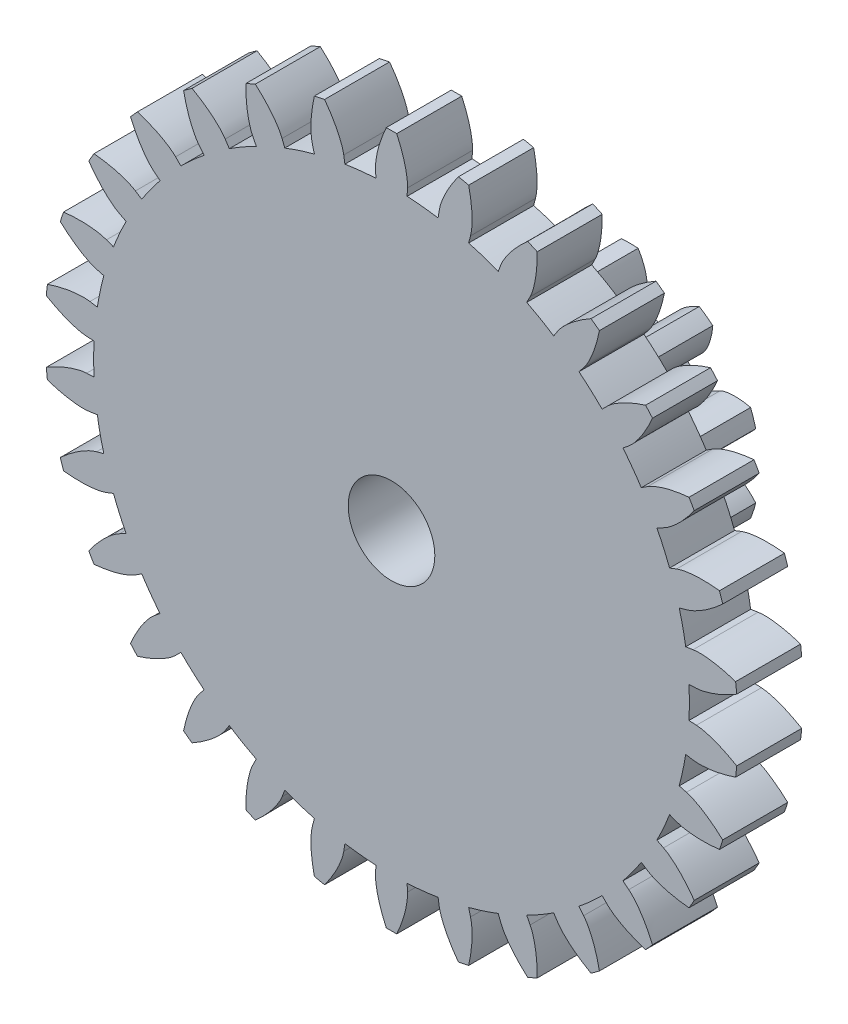
SolidWorks part; units mm, degrees
ref_plane "前视基准面" through (0, 0, 0) normal (0, 0, 1) x (1, 0, 0)
ref_plane "上视基准面" through (0, 0, 0) normal (0, 1, 0) x (1, 0, 0)
ref_plane "右视基准面" through (0, 0, 0) normal (1, 0, 0) x (0, 0, -1)
other "Configuration Table"
sketch "草图1" plane through (0, 0, 0) normal (0, 0, 1) x (1, 0, 0)
  line L0 (0, 0) -> (2.5, 0) construction
  line L1 (0, 0) -> (2.4692, 0.3911) construction
  line L2 (0, 0) -> (2.324, 0.3431)
  line L3 (2.4692, 0.3911) -> (2.4692, -0.3911) construction
  line L4 (0, 0) -> (2.324, -0.3431)
  circle A0 centre (0, 0) radius 3
  circle A1 centre (0, 0) radius 2.5 construction
  circle A2 centre (0, 0) radius 1.875
  circle A3 centre (0, 0) radius 2.3492 construction
  circle A4 centre (0, 0) radius 1
  spline S0 degree 4 poles (2.324, 0.3431) (2.3418, 0.3457) (2.3907, 0.3567) (2.48, 0.3921) (2.6156, 0.4687) (2.774, 0.5944) (2.9524, 0.7829) (3.1261, 1.0328) (3.2755, 1.3318) (3.3905, 1.6731) (3.4623, 2.0258) (3.4939, 2.3843) (3.4875, 2.7617) (3.431, 3.2258) (3.293, 3.7669) (3.0427, 4.3657) (2.6648, 4.9798) (2.2034, 5.533) (1.6708, 6.0186) (1.0824, 6.4323) (0.4456, 6.7712) (-0.2216, 7.0345) (-0.9214, 7.2211) (-1.5352, 7.3195) (-2.0864, 7.356) (-2.4818, 7.3587) (-2.8333, 7.3427) (-3.0656, 7.3237) (-3.3922, 7.2873) (-3.6372, 7.2455) (-3.8821, 7.2011) (-4.0043, 7.1711) (-4.0832, 7.1539) knots 0 0 0 0 0 0.005604 0.015718 0.02996 0.048734 0.068727 0.096889 0.125051 0.153212 0.181374 0.209535 0.237696 0.271429 0.327752 0.384075 0.440398 0.496721 0.553044 0.609367 0.66569 0.722013 0.778336 0.834659 0.86282 0.890982 0.909091 0.931818 0.954545 0.977273 1 1 1 1 1 construction
  spline S1 degree 4 poles (2.324, 0.3431) (2.3418, 0.3457) (2.3907, 0.3567) (2.48, 0.3921) (2.6156, 0.4687) (2.774, 0.5944) (2.9524, 0.7829) (3.1261, 1.0328) (3.2755, 1.3318) (3.3905, 1.6731) (3.4623, 2.0258) (3.4939, 2.3843) (3.4875, 2.7617) (3.431, 3.2258) (3.293, 3.7669) (3.0427, 4.3657) (2.6648, 4.9798) (2.2034, 5.533) (1.6708, 6.0186) (1.0824, 6.4323) (0.4456, 6.7712) (-0.2216, 7.0345) (-0.9214, 7.2211) (-1.5352, 7.3195) (-2.0864, 7.356) (-2.4818, 7.3587) (-2.7511, 7.3465) (-2.8848, 7.3375) (-2.9371, 7.3334) knots 0 0 0 0 0 0.005604 0.015718 0.02996 0.048734 0.068727 0.096889 0.125051 0.153212 0.181374 0.209535 0.237696 0.271429 0.327752 0.384075 0.440398 0.496721 0.553044 0.609367 0.66569 0.722013 0.778336 0.834659 0.86282 0.890982 0.909091 0.909091 0.909091 0.909091 0.909091
  spline S2 degree 4 poles (2.324, -0.3431) (2.3418, -0.3457) (2.3907, -0.3567) (2.48, -0.3921) (2.6156, -0.4687) (2.774, -0.5944) (2.9524, -0.7829) (3.1261, -1.0328) (3.2755, -1.3318) (3.3905, -1.6731) (3.4623, -2.0258) (3.4939, -2.3843) (3.4875, -2.7617) (3.431, -3.2258) (3.293, -3.7669) (3.0427, -4.3657) (2.6648, -4.9798) (2.2034, -5.533) (1.6708, -6.0186) (1.0824, -6.4323) (0.4456, -6.7712) (-0.2216, -7.0345) (-0.9214, -7.2211) (-1.5352, -7.3195) (-2.0864, -7.356) (-2.4818, -7.3587) (-2.8333, -7.3427) (-3.0656, -7.3237) (-3.3922, -7.2873) (-3.6372, -7.2455) (-3.8821, -7.2011) (-4.0043, -7.1711) (-4.0832, -7.1539) knots 0 0 0 0 0 0.005604 0.015718 0.02996 0.048734 0.068727 0.096889 0.125051 0.153212 0.181374 0.209535 0.237696 0.271429 0.327752 0.384075 0.440398 0.496721 0.553044 0.609367 0.66569 0.722013 0.778336 0.834659 0.86282 0.890982 0.909091 0.931818 0.954545 0.977273 1 1 1 1 1 construction
  spline S3 degree 4 poles (2.324, -0.3431) (2.3418, -0.3457) (2.3907, -0.3567) (2.48, -0.3921) (2.6156, -0.4687) (2.774, -0.5944) (2.9524, -0.7829) (3.1261, -1.0328) (3.2755, -1.3318) (3.3905, -1.6731) (3.4623, -2.0258) (3.4939, -2.3843) (3.4875, -2.7617) (3.431, -3.2258) (3.293, -3.7669) (3.0427, -4.3657) (2.6648, -4.9798) (2.2034, -5.533) (1.6708, -6.0186) (1.0824, -6.4323) (0.4456, -6.7712) (-0.2216, -7.0345) (-0.9214, -7.2211) (-1.5352, -7.3195) (-2.0864, -7.356) (-2.4818, -7.3587) (-2.7511, -7.3465) (-2.8848, -7.3375) (-2.9371, -7.3334) knots 0 0 0 0 0 0.005604 0.015718 0.02996 0.048734 0.068727 0.096889 0.125051 0.153212 0.181374 0.209535 0.237696 0.271429 0.327752 0.384075 0.440398 0.496721 0.553044 0.609367 0.66569 0.722013 0.778336 0.834659 0.86282 0.890982 0.909091 0.909091 0.909091 0.909091 0.909091
  point P15 (2.4692, 0)
  dimension "齿顶圆直径" = 6
  dimension "分度圆直径" = 5
  dimension "齿根圆直径" = 3.75
  dimension "基圆直径" = 4.6985
  dimension "内孔直径" = 2
  dimension "渐近线镜像线夹角" = 9
extrude "凸台-拉伸1" add sketch "草图1" along normal blind 4 contours A0 | A4
extrude "切除-拉伸1" cut sketch "草图1<3>" along normal through all contours A2 S3 A0 S1 region at (2.52, 0, 0)
sketch "草图1<3>" plane through (0, 0, 0) normal (0, 0, 1) x (1, 0, 0) same geometry as "草图1"
pattern_circular "阵列(圆周)1" count 10 every 36 about axis through (0, 0, 4) along (0, 0, 1) of "切除-拉伸1"
sketch "草图2" plane through (0, 0, 4) normal (0, 0, 1) x (1, 0, 0)
  line L0 (0, 0) -> (7.5, 0) construction
  line L1 (0, 0) -> (7.038, 0.3688)
  line L2 (0, 0) -> (7.038, -0.3688)
  line L3 (7.038, 0.3688) -> (7.038, -0.3688) construction
  circle A0 centre (0, 0) radius 7.5 construction
  circle A1 centre (0, 0) radius 7.0477 construction
  circle A2 centre (0, 0) radius 6.875
  circle A3 centre (0, 0) radius 8
  circle A4 centre (0, 0) radius 1
  spline S0 degree 4 poles (7.038, -0.3688) (7.0648, -0.3703) (7.1181, -0.3756) (7.2661, -0.4036) (7.54, -0.4903) (7.9387, -0.6789) (8.4412, -1.0177) (9.0178, -1.5414) (9.5944, -2.2492) (10.1095, -3.1096) (10.5312, -4.1044) (10.8266, -5.1431) (11.0027, -6.2081) (11.0697, -7.3387) (11.0063, -8.7398) (10.7169, -10.3898) (10.1042, -12.238) (9.1146, -14.161) (7.8594, -15.921) (6.3787, -17.4949) (4.7097, -18.8667) (3.115, -19.8807) (1.6719, -20.6128) (0.4283, -21.1308) (-0.5886, -21.4897) (-1.622, -21.7931) (-2.6724, -22.0413) (-3.73, -22.2344) (-4.6701, -22.3557) (-5.4675, -22.426) (-6.1046, -22.4596) (-6.5222, -22.4739) (-6.9919, -22.4794) (-7.2978, -22.4782) (-7.7905, -22.469) (-8.174, -22.4512) (-8.6389, -22.4248) (-9.053, -22.3901) (-9.4984, -22.3472) (-9.9204, -22.296) (-10.2509, -22.2515) (-10.4614, -22.2192) (-10.5706, -22.2024) knots 0 0 0 0 0 0.002802 0.005604 0.015718 0.02996 0.048734 0.068727 0.096889 0.125051 0.153212 0.181374 0.209535 0.237696 0.271429 0.327752 0.384075 0.440398 0.496721 0.553044 0.609367 0.66569 0.693852 0.722013 0.750174 0.778336 0.806497 0.834659 0.86282 0.876901 0.890982 0.900036 0.909091 0.920455 0.931818 0.943182 0.954545 0.965909 0.977273 0.988636 1 1 1 1 1 construction
  spline S1 degree 4 poles (7.038, -0.3688) (7.0648, -0.3703) (7.1181, -0.3756) (7.2661, -0.4036) (7.54, -0.4903) (7.9387, -0.6789) (8.4412, -1.0177) (9.0178, -1.5414) (9.5944, -2.2492) (10.1095, -3.1096) (10.5312, -4.1044) (10.8266, -5.1431) (11.0027, -6.2081) (11.0697, -7.3387) (11.0063, -8.7398) (10.7169, -10.3898) (10.1042, -12.238) (9.1146, -14.161) (7.8594, -15.921) (6.3787, -17.4949) (4.7097, -18.8667) (3.115, -19.8807) (1.6719, -20.6128) (0.4283, -21.1308) (-0.5886, -21.4897) (-1.622, -21.7931) (-2.6724, -22.0413) (-3.73, -22.2344) (-4.6701, -22.3557) (-5.4675, -22.426) (-6.1046, -22.4596) (-6.5222, -22.4739) (-6.8693, -22.478) (-7.028, -22.4785) (-7.1067, -22.4783) knots 0 0 0 0 0 0.002802 0.005604 0.015718 0.02996 0.048734 0.068727 0.096889 0.125051 0.153212 0.181374 0.209535 0.237696 0.271429 0.327752 0.384075 0.440398 0.496721 0.553044 0.609367 0.66569 0.693852 0.722013 0.750174 0.778336 0.806497 0.834659 0.86282 0.876901 0.890982 0.900036 0.909091 0.909091 0.909091 0.909091 0.909091
  spline S2 degree 4 poles (7.038, 0.3688) (7.0648, 0.3703) (7.1181, 0.3756) (7.2661, 0.4036) (7.54, 0.4903) (7.9387, 0.6789) (8.4412, 1.0177) (9.0178, 1.5414) (9.5944, 2.2492) (10.1095, 3.1096) (10.5312, 4.1044) (10.8266, 5.1431) (11.0027, 6.2081) (11.0697, 7.3387) (11.0063, 8.7398) (10.7169, 10.3898) (10.1042, 12.238) (9.1146, 14.161) (7.8594, 15.921) (6.3787, 17.4949) (4.7097, 18.8667) (3.115, 19.8807) (1.6719, 20.6128) (0.4283, 21.1308) (-0.5886, 21.4897) (-1.622, 21.7931) (-2.6724, 22.0413) (-3.73, 22.2344) (-4.6701, 22.3557) (-5.4675, 22.426) (-6.1046, 22.4596) (-6.5222, 22.4739) (-6.9919, 22.4794) (-7.2978, 22.4782) (-7.7905, 22.469) (-8.174, 22.4512) (-8.6389, 22.4248) (-9.053, 22.3901) (-9.4984, 22.3472) (-9.9204, 22.296) (-10.2509, 22.2515) (-10.4614, 22.2192) (-10.5706, 22.2024) knots 0 0 0 0 0 0.002802 0.005604 0.015718 0.02996 0.048734 0.068727 0.096889 0.125051 0.153212 0.181374 0.209535 0.237696 0.271429 0.327752 0.384075 0.440398 0.496721 0.553044 0.609367 0.66569 0.693852 0.722013 0.750174 0.778336 0.806497 0.834659 0.86282 0.876901 0.890982 0.900036 0.909091 0.920455 0.931818 0.943182 0.954545 0.965909 0.977273 0.988636 1 1 1 1 1 construction
  spline S3 degree 4 poles (7.038, 0.3688) (7.0648, 0.3703) (7.1181, 0.3756) (7.2661, 0.4036) (7.54, 0.4903) (7.9387, 0.6789) (8.4412, 1.0177) (9.0178, 1.5414) (9.5944, 2.2492) (10.1095, 3.1096) (10.5312, 4.1044) (10.8266, 5.1431) (11.0027, 6.2081) (11.0697, 7.3387) (11.0063, 8.7398) (10.7169, 10.3898) (10.1042, 12.238) (9.1146, 14.161) (7.8594, 15.921) (6.3787, 17.4949) (4.7097, 18.8667) (3.115, 19.8807) (1.6719, 20.6128) (0.4283, 21.1308) (-0.5886, 21.4897) (-1.622, 21.7931) (-2.6724, 22.0413) (-3.73, 22.2344) (-4.6701, 22.3557) (-5.4675, 22.426) (-6.1046, 22.4596) (-6.5222, 22.4739) (-6.8693, 22.478) (-7.028, 22.4785) (-7.1067, 22.4783) knots 0 0 0 0 0 0.002802 0.005604 0.015718 0.02996 0.048734 0.068727 0.096889 0.125051 0.153212 0.181374 0.209535 0.237696 0.271429 0.327752 0.384075 0.440398 0.496721 0.553044 0.609367 0.66569 0.693852 0.722013 0.750174 0.778336 0.806497 0.834659 0.86282 0.876901 0.890982 0.900036 0.909091 0.909091 0.909091 0.909091 0.909091
  point P16 (7.038, 0)
  dimension "内孔直径" = 2
  dimension "分度圆直径" = 15
  dimension "齿顶圆直径" = 16
  dimension "基圆直径" = 14.0954
  dimension "齿根圆直径" = 13.75
  dimension "渐开线镜像线夹角" = 3
extrude "凸台-拉伸2" add sketch "草图2" along normal blind 1.5 contours A3 | A4
extrude "切除-拉伸3" cut sketch "草图2<3>" along normal through all contours S3 L1 A2 L2 S1 A3 region at (7.5024, 0, 4)
sketch "草图2<3>" plane through (0, 0, 4) normal (0, 0, 1) x (1, 0, 0) same geometry as "草图2"
pattern_circular "阵列(圆周)2" count 30 over 360 about axis through (0, 0, 5.5) along (0, 0, 1) of "切除-拉伸3"
equation "\"m\" = 0.5'模数"
equation "\"z\" = 10'齿数"
equation "\"a\"= 20度'压力角"
equation "\"d\"= \"m\" * \"z\"'分度圆直径"
equation "\"da\"= ( \"z\" + 2 ) * \"m\"'齿顶圆直径"
equation "\"df\"= ( \"z\" - 2.5 ) * \"m\"'齿根圆直径"
equation "\"s\"= 0.5 * PI * \"m\"'分度圆齿厚"
equation "\"r\"= 0.38 * \"m\"'齿根圆角"
equation "\"B\"= 0.3 * \"d\"'齿厚"
equation "\"db\"= \"m\" * \"z\" * cos ( \"a\" )'基圆直径"
equation "\"rb\"= \"db\" / 2'基圆半径"
equation "\"齿顶圆直径@草图1\"= \"da\""
equation "\"分度圆直径@草图1\"= \"d\""
equation "\"齿根圆直径@草图1\"= \"df\""
equation "\"基圆直径@草图1\"= \"db\""
equation "\"渐近线镜像线夹角@草图1\"= 360 / 4 / \"z\""
equation "\"h\"= 4'齿轮厚度"
equation "\"ir\"= 2'内孔直径"
equation "\"内孔直径@草图1\"= \"ir\""
equation "\"齿轮厚@凸台-拉伸1\"= \"h\""
equation "\"齿轮夹角@阵列(圆周)1\"= 360 / \"z\""
equation "\"齿数@阵列(圆周)1\"= \"z\""
equation "\"m1\" = 0.5'模数"
equation "\"z1\"= 30'齿数"
equation "\"a1\"= 20度'压力角"
equation "\"d1\"= \"m1\" * \"z1\"'分度圆直径"
equation "\"da1\"= ( \"z1\" + 2 ) * \"m1\"'齿顶圆直径"
equation "\"df1\"= ( \"z1\" - 2.5 ) * \"m1\"'齿根圆直径"
equation "\"s1\"= 0.5 * PI * \"m1\"'分度圆齿厚"
equation "\"r1\"= 0.38 * \"m1\"'齿根圆角"
equation "\"B1\"= 0.3 * \"d1\"'齿厚"
equation "\"db1\"= \"m1\" * \"z1\" * cos ( \"a1\" )'基圆直径"
equation "\"rb1\"= \"db1\" / 2'基圆半径"
equation "\"分度圆直径@草图2\"= \"d1\""
equation "\"齿顶圆直径@草图2\"= \"da1\""
equation "\"基圆直径@草图2\"= \"db1\""
equation "\"齿根圆直径@草图2\"= \"df1\""
equation "\"渐开线镜像线夹角@草图2\"= 360 / 4 / \"z1\""
equation "\"内孔直径@草图2\"= \"ir\""
equation "\"二层齿轮厚@凸台-拉伸2\" = \"h1\""
equation "\"h1\" = 1.5'齿轮厚度"
equation "\"二层齿数@阵列(圆周)2\"= \"z1\""
